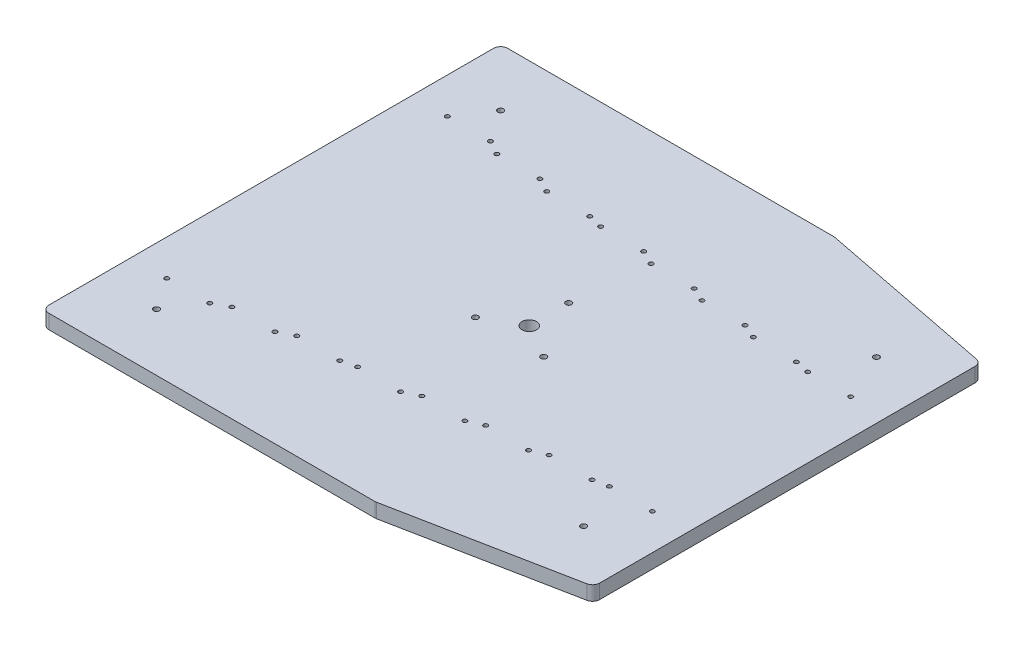
SolidWorks part; units mm, degrees
material "AISI Type 316L stainless steel"
ref_plane "Front Plane" through (0, 0, 0) normal (0, 0, 1) x (1, 0, 0)
ref_plane "Top Plane" through (0, 0, 0) normal (0, 1, 0) x (1, 0, 0)
ref_plane "Right Plane" through (0, 0, 0) normal (1, 0, 0) x (0, 0, -1)
sketch "Sketch1" plane through (0, 0, 0) normal (0, 1, 0) x (1, 0, 0)
  line L1 (-228.6, -203.2) -> (228.6, -203.2)
  line L2 (-228.6, -203.2) -> (-228.6, 203.2)
  line L3 (-228.6, 203.2) -> (228.6, 203.2)
  line L4 (228.6, -203.2) -> (228.6, 203.2)
  line L5 (-228.6, -203.2) -> (228.6, 203.2) construction
  line L6 (-228.6, 203.2) -> (228.6, -203.2) construction
  point P0 (0, 0)
  dimension "D1" = 457.2
  dimension "D2" = 406.4
extrude "Boss-Extrude1" add sketch "Sketch1" along normal blind 12.7
hole_wizard "#6 Clearance Hole1" positions "Sketch2" profile "Sketch3" hole size "#6" standard "ANSI Inch" end condition through all
sketch "Sketch2" plane through (0, 0, 0) normal (0, -1, 0) x (-1, 0, 0)
  line L0 (-228.6, 0) -> (228.6, 0) construction
  line L1 (-228.6, -203.2) -> (-228.6, 203.2) construction
  line L2 (228.6, 203.2) -> (228.6, -203.2) construction
  point P0 (-196.85, 87.8764)
  point P3 (-158.75, 87.8764)
  point P6 (-146.05, 90.4545)
  point P9 (-107.95, 90.4545)
  point P12 (-95.25, 95.8317)
  point P15 (-57.15, 95.8317)
  point P18 (-44.45, 101.5035)
  point P21 (-6.35, 101.5035)
  point P24 (6.35, 107.6173)
  point P27 (44.45, 107.6173)
  point P30 (57.15, 110.711)
  point P33 (95.25, 110.711)
  point P36 (107.95, 117.3404)
  point P39 (146.05, 117.3404)
  point P42 (158.75, 124.2644)
  point P45 (196.85, 124.2644)
  point P56 (196.85, -124.2644)
  point P57 (158.75, -124.2644)
  point P58 (146.05, -117.3404)
  point P59 (107.95, -117.3404)
  point P60 (95.25, -110.711)
  point P61 (57.15, -110.711)
  point P62 (44.45, -107.6173)
  point P63 (6.35, -107.6173)
  point P64 (-6.35, -101.5035)
  point P65 (-44.45, -101.5035)
  point P66 (-57.15, -95.8317)
  point P67 (-95.25, -95.8317)
  point P68 (-107.95, -90.4545)
  point P69 (-146.05, -90.4545)
  point P70 (-158.75, -87.8764)
  point P71 (-196.85, -87.8764)
sketch "Sketch3" plane through (196.85, 0, -87.8764) normal (1, 0, 0) x (0, 0, -1)
  line L0 (0, 0) -> (0, 12.7)
  line L1 (0, 12.7) -> (1.8986, 12.7)
  line L2 (1.8986, 12.7) -> (1.8986, 0)
  line L5 (1.8986, 0) -> (0, 0)
  line L11 (0, -6.35) -> (0, 107.95) construction
  dimension "Thru Hole Dia." = 3.7973
  dimension "Thru Hole Depth" = 12.7
sketch "Sketch4" plane through (0, 12.7, 0) normal (0, 1, 0) x (1, 0, 0)
  line L0 (-196.85, 124.2644) -> (-158.75, 124.2644) construction
  line L1 (-196.85, 130.6144) -> (-158.75, 130.6144)
  line L2 (-196.85, 117.9144) -> (-158.75, 117.9144)
  line L3 (-146.05, 117.3404) -> (-107.95, 117.3404) construction
  line L4 (-146.05, 123.6904) -> (-107.95, 123.6904)
  line L5 (-146.05, 110.9904) -> (-107.95, 110.9904)
  line L6 (-95.25, 110.711) -> (-57.15, 110.711) construction
  line L7 (-95.25, 117.061) -> (-57.15, 117.061)
  line L8 (-95.25, 104.361) -> (-57.15, 104.361)
  line L9 (-44.45, 107.6173) -> (-6.35, 107.6173) construction
  line L10 (-44.45, 113.9673) -> (-6.35, 113.9673)
  line L11 (-44.45, 101.2673) -> (-6.35, 101.2673)
  line L12 (6.35, 101.5035) -> (44.45, 101.5035) construction
  line L13 (6.35, 107.8535) -> (44.45, 107.8535)
  line L14 (6.35, 95.1535) -> (44.45, 95.1535)
  line L15 (57.15, 95.8317) -> (95.25, 95.8317) construction
  line L16 (57.15, 102.1817) -> (95.25, 102.1817)
  line L17 (57.15, 89.4817) -> (95.25, 89.4817)
  line L18 (107.95, 90.4545) -> (146.05, 90.4545) construction
  line L19 (107.95, 96.8045) -> (146.05, 96.8045)
  line L20 (107.95, 84.1045) -> (146.05, 84.1045)
  line L21 (158.75, 87.8764) -> (196.85, 87.8764) construction
  line L22 (158.75, 94.2264) -> (196.85, 94.2264)
  line L23 (158.75, 81.5264) -> (196.85, 81.5264)
  line L24 (-228.6, 0) -> (228.6, 0) construction
  line L25 (-228.6, 203.2) -> (-228.6, -203.2) construction
  line L26 (228.6, -203.2) -> (228.6, 203.2) construction
  line L27 (-196.85, -124.2644) -> (-158.75, -124.2644) construction
  line L28 (-196.85, -130.6144) -> (-158.75, -130.6144)
  line L29 (-196.85, -117.9144) -> (-158.75, -117.9144)
  line L30 (-146.05, -117.3404) -> (-107.95, -117.3404) construction
  line L31 (-146.05, -123.6904) -> (-107.95, -123.6904)
  line L32 (-146.05, -110.9904) -> (-107.95, -110.9904)
  line L33 (-95.25, -110.711) -> (-57.15, -110.711) construction
  line L34 (-95.25, -117.061) -> (-57.15, -117.061)
  line L35 (-95.25, -104.361) -> (-57.15, -104.361)
  line L36 (-44.45, -107.6173) -> (-6.35, -107.6173) construction
  line L37 (-44.45, -113.9673) -> (-6.35, -113.9673)
  line L38 (-44.45, -101.2673) -> (-6.35, -101.2673)
  line L39 (6.35, -101.5035) -> (44.45, -101.5035) construction
  line L40 (6.35, -107.8535) -> (44.45, -107.8535)
  line L41 (6.35, -95.1535) -> (44.45, -95.1535)
  line L42 (57.15, -95.8317) -> (95.25, -95.8317) construction
  line L43 (57.15, -102.1817) -> (95.25, -102.1817)
  line L44 (57.15, -89.4817) -> (95.25, -89.4817)
  line L45 (107.95, -90.4545) -> (146.05, -90.4545) construction
  line L46 (107.95, -96.8045) -> (146.05, -96.8045)
  line L47 (107.95, -84.1045) -> (146.05, -84.1045)
  line L48 (158.75, -87.8764) -> (196.85, -87.8764) construction
  line L49 (158.75, -94.2264) -> (196.85, -94.2264)
  line L50 (158.75, -81.5264) -> (196.85, -81.5264)
  arc A0 (-196.85, 130.6144) -> (-196.85, 117.9144) centre (-196.85, 124.2644) ccw
  arc A1 (-158.75, 117.9144) -> (-158.75, 130.6144) centre (-158.75, 124.2644) ccw
  arc A2 (-146.05, 123.6904) -> (-146.05, 110.9904) centre (-146.05, 117.3404) ccw
  arc A3 (-107.95, 110.9904) -> (-107.95, 123.6904) centre (-107.95, 117.3404) ccw
  arc A6 (-95.25, 117.061) -> (-95.25, 104.361) centre (-95.25, 110.711) ccw
  arc A7 (-57.15, 104.361) -> (-57.15, 117.061) centre (-57.15, 110.711) ccw
  arc A8 (-44.45, 113.9673) -> (-44.45, 101.2673) centre (-44.45, 107.6173) ccw
  arc A9 (-6.35, 101.2673) -> (-6.35, 113.9673) centre (-6.35, 107.6173) ccw
  arc A10 (6.35, 107.8535) -> (6.35, 95.1535) centre (6.35, 101.5035) ccw
  arc A11 (44.45, 95.1535) -> (44.45, 107.8535) centre (44.45, 101.5035) ccw
  arc A12 (57.15, 102.1817) -> (57.15, 89.4817) centre (57.15, 95.8317) ccw
  arc A13 (95.25, 89.4817) -> (95.25, 102.1817) centre (95.25, 95.8317) ccw
  arc A14 (107.95, 96.8045) -> (107.95, 84.1045) centre (107.95, 90.4545) ccw
  arc A15 (146.05, 84.1045) -> (146.05, 96.8045) centre (146.05, 90.4545) ccw
  arc A16 (158.75, 94.2264) -> (158.75, 81.5264) centre (158.75, 87.8764) ccw
  arc A17 (196.85, 81.5264) -> (196.85, 94.2264) centre (196.85, 87.8764) ccw
  circle A22 centre (196.85, 87.8764) radius 1.8987 construction
  arc A27 (-196.85, -130.6144) -> (-196.85, -117.9144) centre (-196.85, -124.2644) cw
  arc A28 (-158.75, -117.9144) -> (-158.75, -130.6144) centre (-158.75, -124.2644) cw
  arc A29 (-146.05, -123.6904) -> (-146.05, -110.9904) centre (-146.05, -117.3404) cw
  arc A30 (-107.95, -110.9904) -> (-107.95, -123.6904) centre (-107.95, -117.3404) cw
  arc A31 (-95.25, -117.061) -> (-95.25, -104.361) centre (-95.25, -110.711) cw
  arc A32 (-57.15, -104.361) -> (-57.15, -117.061) centre (-57.15, -110.711) cw
  arc A33 (-44.45, -113.9673) -> (-44.45, -101.2673) centre (-44.45, -107.6173) cw
  arc A34 (-6.35, -101.2673) -> (-6.35, -113.9673) centre (-6.35, -107.6173) cw
  arc A35 (6.35, -107.8535) -> (6.35, -95.1535) centre (6.35, -101.5035) cw
  arc A36 (44.45, -95.1535) -> (44.45, -107.8535) centre (44.45, -101.5035) cw
  arc A37 (57.15, -102.1817) -> (57.15, -89.4817) centre (57.15, -95.8317) cw
  arc A38 (95.25, -89.4817) -> (95.25, -102.1817) centre (95.25, -95.8317) cw
  arc A39 (107.95, -96.8045) -> (107.95, -84.1045) centre (107.95, -90.4545) cw
  arc A40 (146.05, -84.1045) -> (146.05, -96.8045) centre (146.05, -90.4545) cw
  arc A41 (158.75, -94.2264) -> (158.75, -81.5264) centre (158.75, -87.8764) cw
  arc A42 (196.85, -81.5264) -> (196.85, -94.2264) centre (196.85, -87.8764) cw
  point P4 (-177.8, 124.2644)
  point P16 (-127, 117.3404)
  point P27 (-76.2, 110.711)
  point P32 (-25.4, 107.6173)
  point P41 (25.4, 101.5035)
  point P50 (76.2, 95.8317)
  point P59 (127, 90.4545)
  point P68 (177.8, 87.8764)
  point P96 (-177.8, -124.2644)
  point P103 (-127, -117.3404)
  point P110 (-76.2, -110.711)
  point P117 (-25.4, -107.6173)
  point P124 (25.4, -101.5035)
  point P131 (76.2, -95.8317)
  point P138 (127, -90.4545)
  point P145 (177.8, -87.8764)
extrude "Cut-Extrude1" [suppressed] cut sketch "Sketch4" against normal blind 3.175
sketch "Sketch5" plane through (0, 0, 0) normal (0, -1, 0) x (1, 0, 0)
  line L0 (-228.6, -203.2) -> (228.6, 203.2) construction
  circle A0 centre (0, 0) radius 6.4135
  dimension "D1" = 12.827
extrude "Cut-Extrude2" cut sketch "Sketch5" against normal through all
sketch "Sketch6" plane through (0, 0, 0) normal (0, -1, 0) x (1, 0, 0)
  line L0 (-228.6, -203.2) -> (-228.6, 203.2) construction
  line L1 (-192.913, -121.9914) -> (-196.85, -119.7184)
  line L2 (-196.85, -119.7184) -> (-200.787, -121.9914)
  line L3 (-200.787, -121.9914) -> (-200.787, -126.5374)
  line L4 (-200.787, -126.5374) -> (-196.85, -128.8105)
  line L5 (-196.85, -128.8105) -> (-192.913, -126.5374)
  line L6 (-192.913, -126.5374) -> (-192.913, -121.9914)
  circle A0 centre (-196.85, -124.2644) radius 3.937 construction
  dimension "D1" = 7.874
extrude "Cut-Extrude3" cut sketch "Sketch6" against normal blind 3.175
pattern_sketch "Sketch-Pattern1" of "Cut-Extrude3" driven by "Sketch2"
hole_wizard "#10 Clearance Hole1" positions "Sketch7" profile "Sketch9" hole size "#10" standard "ANSI Inch" end condition through all
sketch "Sketch7" plane through (0, 12.7, 0) normal (0, 1, 0) x (1, 0, 0)
  line L0 (0, 0) -> (0, 34.925) construction
  line L5 (0, 0) -> (30.2459, -17.4625) construction
  line L6 (0, 0) -> (-30.2459, -17.4625) construction
  circle A0 centre (0, 0) radius 34.925 construction
  point P8 (0, 34.925)
  point P28 (30.2459, -17.4625)
  point P29 (-30.2459, -17.4625)
  dimension "D1" = 69.85
sketch "Sketch9" plane through (-30.2459, 12.7, 17.4625) normal (1, 0, 0) x (0, 0, 1)
  line L0 (0, 0) -> (0, 12.7)
  line L1 (0, 12.7) -> (2.5527, 12.7)
  line L2 (2.5527, 12.7) -> (2.5527, 0)
  line L5 (2.5527, 0) -> (0, 0)
  line L11 (0, -6.35) -> (0, 107.95) construction
  dimension "Thru Hole Dia." = 5.1054
  dimension "Thru Hole Depth" = 12.7
sketch "Sketch10" plane through (0, 12.7, 0) normal (0, 1, 0) x (1, 0, 0)
  line L0 (67.0352, -203.2) -> (228.6, -171.45)
  line L1 (-228.6, -203.2) -> (228.6, -203.2) construction
  line L2 (228.6, -203.2) -> (228.6, 203.2) construction
  line L3 (228.6, -171.45) -> (228.6, -203.2)
  line L4 (228.6, -203.2) -> (67.0352, -203.2)
  line L5 (228.6, 0) -> (-228.6, 0) construction
  line L6 (-228.6, 203.2) -> (-228.6, -203.2) construction
  line L7 (228.6, 203.2) -> (67.0352, 203.2)
  line L8 (228.6, 171.45) -> (228.6, 203.2)
  line L9 (67.0352, 203.2) -> (228.6, 171.45)
  circle A0 centre (196.85, 87.8764) radius 1.8987 construction
  dimension "D1" = 31.75
extrude "Cut-Extrude4" cut sketch "Sketch10" against normal through all
fillet "Fillet1" radius 6.35 6 edges at (-228.6, 6.35, 203.2) (-228.6, 6.35, -203.2) (228.6, 6.35, -171.45) (228.6, 6.35, 171.45) (67.0352, 6.35, -203.2) (67.0352, 6.35, 203.2)
hole_wizard "#10 Clearance Hole2" positions "Sketch11" profile "Sketch12" hole size "#10" standard "ANSI Inch" end condition through all
sketch "Sketch11" plane through (0, 12.7, 0) normal (0, 1, 0) x (1, 0, 0)
  line L9 (-222.25, -203.2) -> (66.4172, -203.2) construction
  line L11 (-228.6, 196.85) -> (-228.6, -196.85) construction
  line L12 (228.6, -166.2264) -> (228.6, 166.2264) construction
  line L14 (223.4745, -172.4572) -> (67.6417, -203.0808) construction
  line L16 (228.6, 0) -> (-228.6, 0) construction
  point P39 (177.8, -129.6614)
  point P41 (-177.8, -152.4)
  point P67 (-177.8, 152.4)
  point P68 (177.8, 129.6614)
  dimension "D1" = 50.8
  dimension "D2" = 50.8
  dimension "D3" = 50.8
  dimension "D4" = 50.8
sketch "Sketch12" plane through (177.8, 12.7, 129.6614) normal (1, 0, 0) x (0, 0, 1)
  line L0 (0, 0) -> (0, 12.7)
  line L1 (0, 12.7) -> (2.5527, 12.7)
  line L2 (2.5527, 12.7) -> (2.5527, 0)
  line L5 (2.5527, 0) -> (0, 0)
  line L11 (0, -6.35) -> (0, 107.95) construction
  dimension "Thru Hole Dia." = 5.1054
  dimension "Thru Hole Depth" = 12.7
